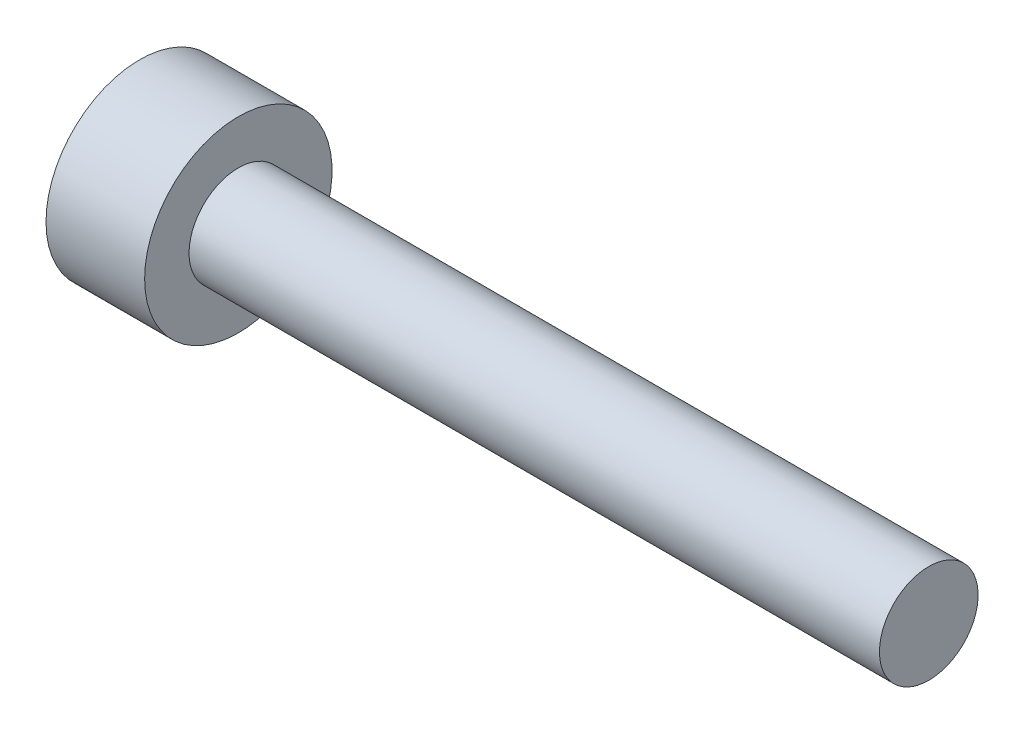
SolidWorks part; units mm, degrees
ref_plane "Front Plane" through (0, 0, 0) normal (0, 0, 1) x (1, 0, 0)
ref_plane "Top Plane" through (0, 0, 0) normal (0, 1, 0) x (1, 0, 0)
ref_plane "Right Plane" through (0, 0, 0) normal (1, 0, 0) x (0, 0, -1)
sketch "Screw Sketch" plane through (0, 0, 0) normal (0, 0, 1) x (1, 0, 0)
  line L0 (-1000, 0) -> (1000, 0) construction
  line L1 (-2, 0) -> (-2, 1.9)
  line L2 (-2, 1.9) -> (0, 1.9)
  line L3 (0, 1.9) -> (0, 1)
  line L4 (0, 1) -> (14, 1)
  line L5 (14, 1) -> (14, 0)
  line L6 (14, 0) -> (-2, 0)
revolve "Screw" add sketch "Screw Sketch" angle 360 about L0
ref_axis "Engine Axis" through (14.8, 0, 0) along (-1, 0, 0)
ref_plane "Head Top" through (-2, 0, 0) normal (1, 0, 0) x (0, 0, -1)
sketch "Socket Sketch" plane through (-2, 0, 0) normal (1, 0, 0) x (0, 0, -1)
  line L0 (0.866, 0) -> (0.433, 0.75)
  line L1 (0.433, 0.75) -> (-0.433, 0.75)
  line L2 (-0.433, 0.75) -> (-0.866, 0)
  line L3 (-0.866, 0) -> (-0.433, -0.75)
  line L4 (-0.433, -0.75) -> (0.433, -0.75)
  line L5 (0.433, -0.75) -> (0.866, 0)
extrude "Socket" cut sketch "Socket Sketch" along normal blind 1
